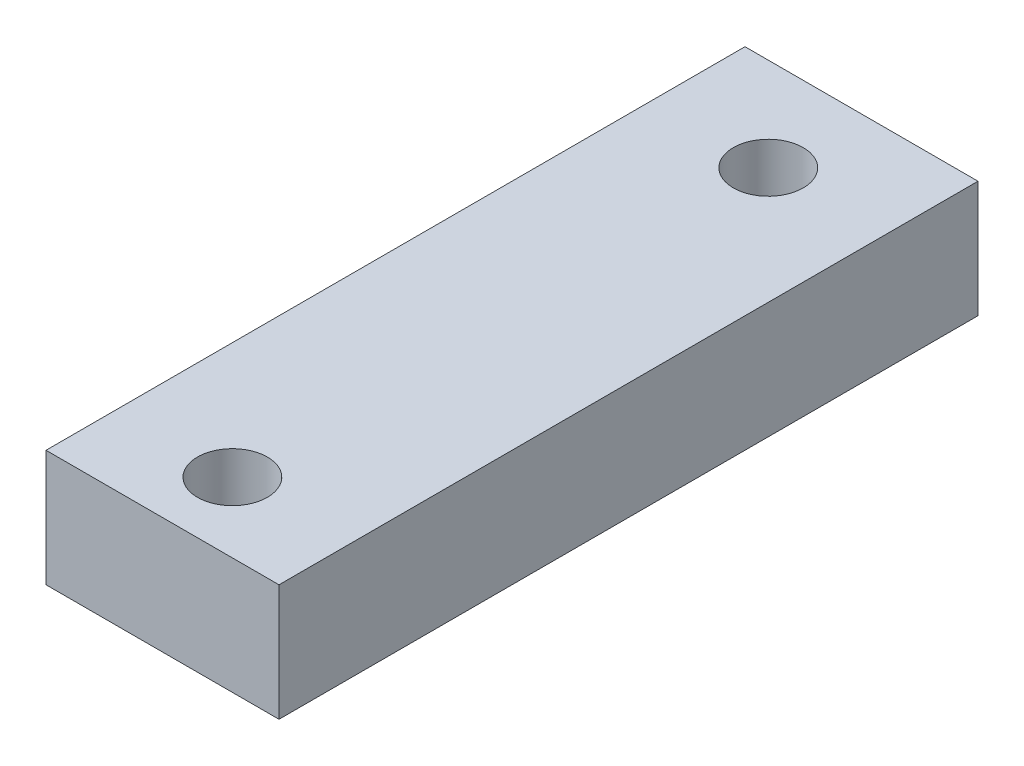
SolidWorks part; units mm, degrees
ref_plane "Piano frontale" through (0, 0, 0) normal (0, 0, 1) x (1, 0, 0)
ref_plane "Piano superiore" through (0, 0, 0) normal (0, 1, 0) x (1, 0, 0)
ref_plane "Piano destro" through (0, 0, 0) normal (1, 0, 0) x (0, 0, -1)
sketch "Schizzo1" plane through (0, 0, 0) normal (0, 0, 1) x (1, 0, 0)
  line L0 (0, 0) -> (-10, 0)
  line L1 (-10, 0) -> (-10, 5)
  line L2 (-10, 5) -> (0, 5)
  line L3 (0, 5) -> (0, 0)
  dimension "D1" = 10
  dimension "D2" = 5
extrude "Estrusione-Estrusione1" add sketch "Schizzo1" along normal blind 30
sketch "Schizzo2" plane through (0, 0, 0) normal (0, -1, 0) x (-1, 0, 0)
  line L0 (10, 0) -> (0, 0) construction
  line L1 (5, -30) -> (5, 3.3709) construction
  line L2 (10, -30) -> (0, -30) construction
  circle A0 centre (5, -27) radius 1.5
  circle A1 centre (5, -4) radius 1.5
  dimension "D3" = 3
  dimension "D1" = 23
  dimension "D2" = 4
extrude "Taglio-Estrusione1" cut sketch "Schizzo2" against normal through all
